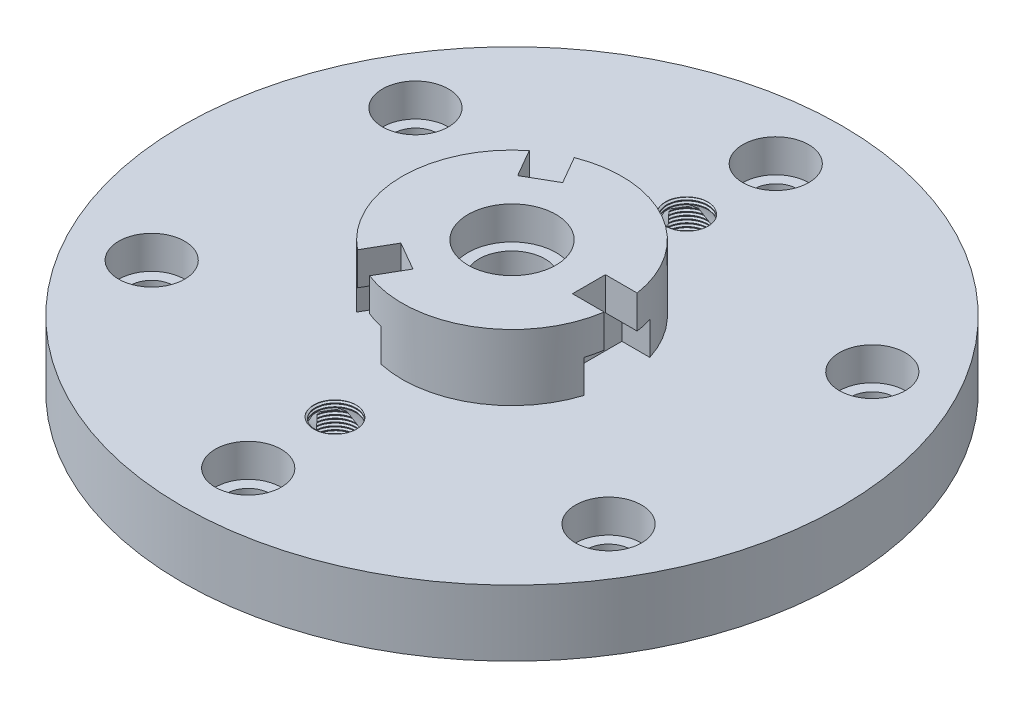
SolidWorks part; units mm, degrees
ref_plane "Front Plane" through (0, 0, 0) normal (0, 0, 1) x (1, 0, 0)
ref_plane "Top Plane" through (0, 0, 0) normal (0, 1, 0) x (1, 0, 0)
ref_plane "Right Plane" through (0, 0, 0) normal (1, 0, 0) x (0, 0, -1)
sketch "Sketch1" plane through (0, 0, 0) normal (0, 0, 1) x (1, 0, 0)
  line L0 (0, 0) -> (30, 0)
  line L1 (30, 0) -> (30, 50)
  line L2 (30, 50) -> (60, 50)
  line L3 (60, 50) -> (60, 70)
  line L4 (60, 70) -> (150, 70)
  line L5 (150, 70) -> (150, 100)
  line L6 (150, 100) -> (0, 100)
  line L7 (0, 100) -> (0, 0)
  dimension "D1" = 30
  dimension "D2" = 30
  dimension "D3" = 50
  dimension "D4" = 20
  dimension "D5" = 60
  dimension "D6" = 150
revolve "Revolve1" add sketch "Sketch1" angle 360 about L7
sketch "Sketch2" plane through (0, 100, 0) normal (0, 1, 0) x (1, 0, 0)
  circle A0 centre (0, 0) radius 50
  dimension "D1" = 100
extrude "Boss-Extrude1" add sketch "Sketch2" along normal blind 30
hole_wizard "CBORE for M5 Hex Head Bolt1" positions "Sketch3" profile "Sketch5" counterbore size "M5" standard "ISO" end condition through all
sketch "Sketch3" plane through (0, 130, 0) normal (0, 1, 0) x (1, 0, 0)
  point P0 (0, 0)
sketch "Sketch5" plane through (0, 130, 0) normal (1, 0, 0) x (0, 0, 1)
  line L0 (0, 0) -> (0, 130)
  line L1 (0, 130) -> (15, 130)
  line L3 (15, 130) -> (15, 15)
  line L4 (15, 15) -> (20, 15)
  line L5 (20, 15) -> (20, 0)
  line L7 (20, 0) -> (0, 0)
  line L11 (0, -6.35) -> (0, 107.95) construction
  dimension "Thru Hole Dia." = 30
  dimension "Thru Hole Depth" = 130
  dimension "C'Bore Dia." = 40
  dimension "C'Bore Depth" = 15
hole_wizard "CBORE for M5 Hex Head Bolt2" positions "Sketch7" profile "Sketch8" counterbore size "M5" standard "ISO" end condition through all
sketch "Sketch7" plane through (0, 100, 0) normal (0, 1, 0) x (1, 0, 0)
  point P0 (0, 120)
  dimension "D1" = 120
sketch "Sketch8" plane through (0, 100, -120) normal (1, 0, 0) x (0, 0, 1)
  line L0 (0, 0) -> (0, 100)
  line L1 (0, 100) -> (10, 100)
  line L3 (10, 100) -> (10, 15)
  line L4 (10, 15) -> (15, 15)
  line L5 (15, 15) -> (15, 0)
  line L7 (15, 0) -> (0, 0)
  line L11 (0, -6.35) -> (0, 107.95) construction
  dimension "Thru Hole Dia." = 20
  dimension "Thru Hole Depth" = 100
  dimension "C'Bore Dia." = 30
  dimension "C'Bore Depth" = 15
pattern_circular "CirPattern1" count 6 over 360 about axis through (0, 130, 0) along (0, 1, 0) of "CBORE for M5 Hex Head Bolt2" reverse direction yes
sketch "Sketch12" plane through (0, 100, 0) normal (0, 1, 0) x (1, 0, 0)
  line L1 (35, 15) -> (92.372, 15)
  line L2 (35, 15) -> (35, -15)
  line L3 (35, -15) -> (92.372, -15)
  line L4 (92.372, 15) -> (92.372, -15)
  dimension "D1" = 30
  dimension "D2" = 35
  dimension "D3" = 15
extrude "Cut-Extrude3" cut sketch "Sketch12" along normal blind 15 contours L1 L4 L3 L2
sketch "Sketch13" plane through (0, 130, 0) normal (0, 1, 0) x (1, 0, 0)
  line L0 (0, -71.5) -> (0, 71.5) construction
  line L1 (35, 7.5) -> (95.861, 7.5)
  line L2 (35, 7.5) -> (35, -7.5)
  line L3 (35, -7.5) -> (95.861, -7.5)
  line L4 (95.861, 7.5) -> (95.861, -7.5)
  dimension "D1" = 15
  dimension "D2" = 35
  dimension "D3" = 7.5
extrude "Cut-Extrude4" cut sketch "Sketch13" against normal blind 15 contours L1 L4 L3 L2
pattern_circular "CirPattern2" count 3 over 360 about axis through (0, 130, 0) along (0, -1, 0) of "Cut-Extrude3"
pattern_circular "CirPattern4" count 3 over 360 about axis through (0, 130, 0) along (0, -1, 0) of "Cut-Extrude4"
sketch "Sketch14" plane through (0, 0, 0) normal (1, 0, 0) x (0, 0, -1)
  line L0 (0, 30) -> (0, -35.3505) construction
  line L1 (8, 30) -> (8, -35.3505)
  line L2 (-8, 30) -> (-8, -35.3505)
  arc A0 (8, 30) -> (-8, 30) centre (0, 30) ccw
  arc A1 (-8, -35.3505) -> (8, -35.3505) centre (0, -35.3505) ccw
  point P3 (0, -2.6752)
  dimension "D1" = 30
  dimension "D2" = 16
ref_plane "Plane1" through (35, 0, 0) normal (1, 0, 0) x (0, 0, -1)
sketch "Sketch15" plane through (35, 0, 0) normal (1, 0, 0) x (0, 0, -1)
  line L0 (0, 30) -> (0, -36.5306) construction
  line L1 (8, 30) -> (8, -36.5306)
  line L2 (-8, 30) -> (-8, -36.5306)
  arc A0 (8, 30) -> (-8, 30) centre (0, 30) ccw
  arc A1 (-8, -36.5306) -> (8, -36.5306) centre (0, -36.5306) ccw
  point P3 (0, -3.2653)
  dimension "D1" = 30
  dimension "D2" = 16
extrude "Cut-Extrude5" cut sketch "Sketch15" against normal blind 15
mirror "Mirror1" about plane through (0, 0, 0) normal (1, 0, 0) of "Cut-Extrude5"
hole_wizard "Tap Drill for M20x1.5 Tap1" positions "Sketch16" profile "Sketch18" hole size "M20x1.5" standard "ISO" end condition through all
sketch "Sketch16" plane through (0, 130, 0) normal (0, 1, 0) x (1, 0, 0)
  point P0 (0, 80)
  point P2 (0, -80)
  point P6 (0, 0)
  dimension "D1" = 160
  dimension "D2" = 80
sketch "Sketch18" plane through (0, 130, -80) normal (1, 0, 0) x (0, 0, 1)
  line L0 (0, 0) -> (0, 130)
  line L1 (0, 130) -> (9.25, 130)
  line L2 (9.25, 130) -> (9.25, 0)
  line L5 (9.25, 0) -> (0, 0)
  line L11 (0, -6.35) -> (0, 107.95) construction
  dimension "Thru Hole Dia." = 18.5
  dimension "Thru Hole Depth" = 130
thread "Thread1" pitch 1.5 method cut profile "Thread Profile1" start angle 0, offset 2, length 40, pitch 1.5, diameter 18.5
ref_plane "Plane2" through (-9.25, 102, 80) normal (0, 0, 1) x (-1, 0, 0)
sketch "Thread Profile1" plane through (-9.25, 102, 80) normal (0, 0, 1) x (-1, 0, 0)
  line L0 (0, 0) -> (0, 1.5) construction
  line L1 (0, 0) -> (0.8119, 0.4687)
  line L2 (0.8119, 0.4687) -> (0.8119, 0.6562)
  line L3 (0.8119, 0.6562) -> (0, 1.125)
  line L4 (0.8119, 0.5625) -> (0, 0.5625) construction
  line L11 (0, 0) -> (0, 1.125)
  point P2 (0, 0)
  dimension "Pitch" = 1.5
  dimension "Profile_Angle" = 60
  dimension "Profile_Land" = 0.1875
  dimension "Profile_Height" = 0.8119
thread "Thread2" pitch 1.5 method cut profile "Thread Profile2" start angle 0, offset 2, length 40, pitch 1.5, diameter 18.5
ref_plane "Plane3" through (-9.25, 102, -80) normal (0, 0, 1) x (-1, 0, 0)
sketch "Thread Profile2" plane through (-9.25, 102, -80) normal (0, 0, 1) x (-1, 0, 0)
  line L0 (0, 0) -> (0, 1.5) construction
  line L1 (0, 0) -> (0.8119, 0.4687)
  line L2 (0.8119, 0.4687) -> (0.8119, 0.6562)
  line L3 (0.8119, 0.6562) -> (0, 1.125)
  line L4 (0.8119, 0.5625) -> (0, 0.5625) construction
  line L11 (0, 0) -> (0, 1.125)
  point P2 (0, 0)
  dimension "Pitch" = 1.5
  dimension "Profile_Angle" = 60
  dimension "Profile_Land" = 0.1875
  dimension "Profile_Height" = 0.8119
